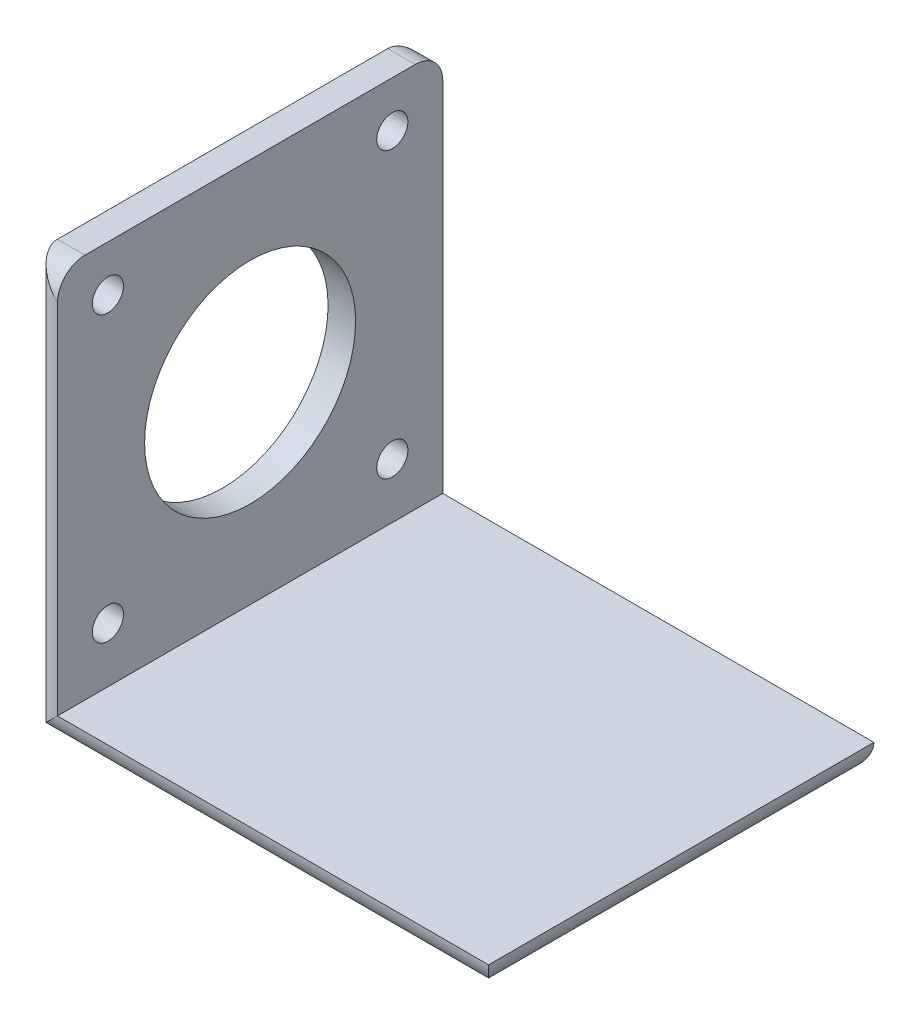
SolidWorks part; units mm, degrees
material "6061 Alloy"
ref_plane "Front Plane" through (0, 0, 0) normal (0, 0, 1) x (1, 0, 0)
ref_plane "Top Plane" through (0, 0, 0) normal (0, 1, 0) x (1, 0, 0)
ref_plane "Right Plane" through (0, 0, 0) normal (1, 0, 0) x (0, 0, -1)
sketch "Sketch1" plane through (0, 0, 0) normal (0, 0, 1) x (1, 0, 0)
  line L0 (0, 0) -> (0, 45)
  line L1 (0, 0) -> (50, 0)
  line L2 (0, 45) -> (3, 45)
  line L3 (3, 45) -> (3, 3)
  line L4 (3, 3) -> (50, 3)
  line L5 (50, 3) -> (50, 0)
  dimension "D1" = 45
  dimension "D2" = 3
  dimension "D3" = 3
  dimension "D4" = 50
extrude "Boss-Extrude1" add sketch "Sketch1" along normal mid plane 42
fillet "Fillet1" radius 3 7 edges at (0, 22.5, -21) (25, 0, -21) (50, 0, 0) (0, 22.5, 21) (25, 0, 21) (1.5, 45, -21) (1.5, 45, 21)
sketch "Sketch2" plane through (3, 0, 0) normal (1, 0, 0) x (0, 0, -1)
  line L0 (0, 45) -> (0, 3) construction
  line L1 (-18, 45) -> (18, 45) construction
  line L2 (-21, 3) -> (21, 3) construction
  line L3 (-21, 24.5) -> (21, 24.5) construction
  line L4 (-21, 3) -> (-21, 42) construction
  line L5 (21, 3) -> (21, 42) construction
  circle A0 centre (0, 24) radius 11.5
  circle A1 centre (-15.5, 40) radius 1.7
  circle A2 centre (-15.5, 9) radius 1.7
  circle A3 centre (15.5, 9) radius 1.7
  circle A4 centre (15.5, 40) radius 1.7
  point P22 (0, 0)
  point P23 (0, 0)
  dimension "D1" = 23
  dimension "D2" = 3.4
  dimension "D5" = 5
  dimension "D3" = 31
  dimension "D4" = 31
extrude "Cut-Extrude2" cut sketch "Sketch2" against normal through all
